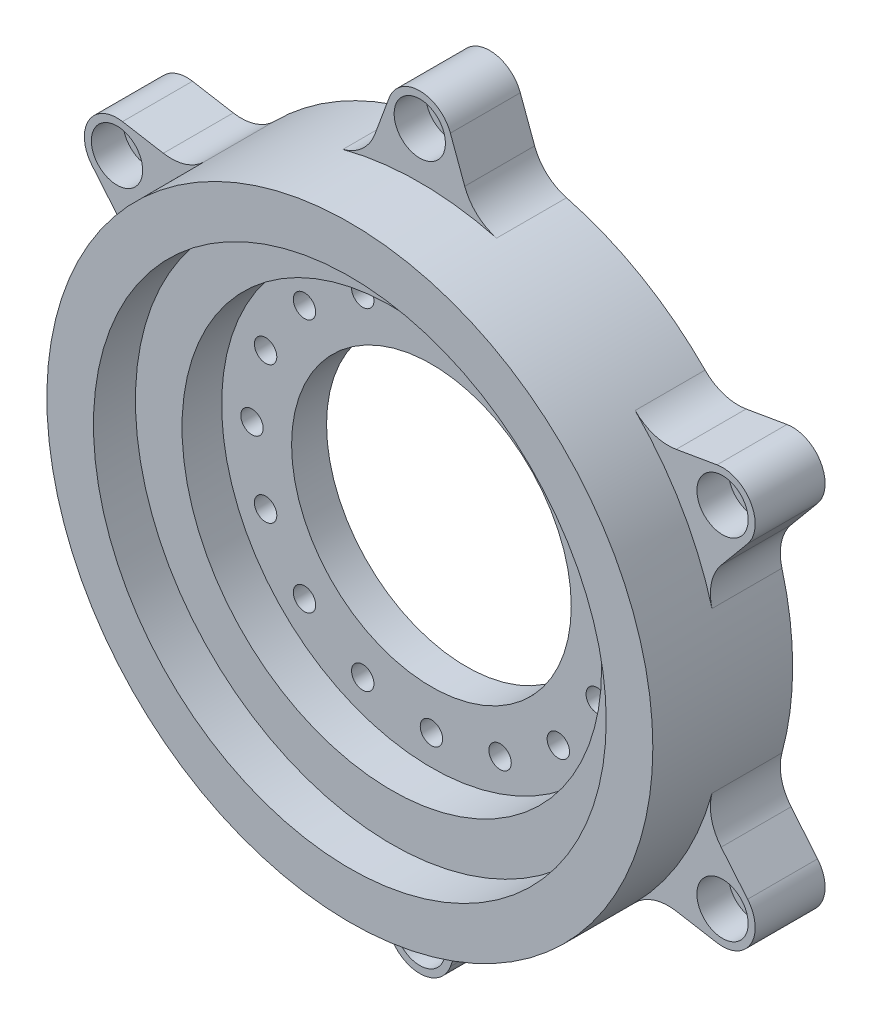
SolidWorks part; units mm, degrees
ref_plane "前视基准面" through (0, 0, 0) normal (0, 0, 1) x (1, 0, 0)
ref_plane "上视基准面" through (0, 0, 0) normal (0, 1, 0) x (1, 0, 0)
ref_plane "右视基准面" through (0, 0, 0) normal (1, 0, 0) x (0, 0, -1)
sketch "草图1" plane through (0, 0, 0) normal (0, 0, 1) x (1, 0, 0)
  circle A0 centre (0, 0) radius 65
  dimension "D1" = 130
extrude "凸台-拉伸1" add sketch "草图1" along normal blind 30
sketch "草图2" plane through (0, 0, 30) normal (0, 0, 1) x (1, 0, 0)
  circle A0 centre (0, 0) radius 55
  dimension "D1" = 110
extrude "切除-拉伸1" cut sketch "草图2" against normal blind 9
sketch "草图3" plane through (0, 0, 21) normal (0, 0, 1) x (1, 0, 0)
  circle A0 centre (0, 0) radius 45
  dimension "D1" = 90
extrude "切除-拉伸2" cut sketch "草图3" against normal blind 8.5
sketch "草图4" plane through (0, 0, 12.5) normal (0, 0, 1) x (1, 0, 0)
  circle A0 centre (0, 0) radius 30
  dimension "D1" = 60
extrude "切除-拉伸3" cut sketch "草图4" against normal blind 8.5
sketch "草图5" plane through (0, 0, 0) normal (0, 0, -1) x (-1, 0, 0)
  circle A0 centre (0, 0) radius 45
  dimension "D1" = 90
extrude "切除-拉伸4" cut sketch "草图5" against normal blind 5
hole_wizard "打孔尺寸(%根据)内六角圆柱头螺钉的类型1" positions "草图8" profile "草图7" counterbore size "M4" standard "GB" end condition through all
sketch "草图8" plane through (0, 0, 5) normal (0, 0, -1) x (-1, 0, 0)
  line L0 (0, 0) -> (0, 67.8808) construction
  circle A0 centre (0, 0) radius 38.5 construction
  point P0 (0, 38.5)
  dimension "D1" = 77
sketch "草图7" plane through (0, 38.5, 5) normal (1, 0, 0) x (0, 1, 0)
  line L0 (0, 0) -> (0, 25)
  line L1 (0, 25) -> (2.4, 25)
  line L3 (2.4, 25) -> (2.4, 1)
  line L4 (2.4, 1) -> (4, 1)
  line L5 (4, 1) -> (4, 0)
  line L7 (4, 0) -> (0, 0)
  line L11 (0, -6.35) -> (0, 107.95) construction
  dimension "通孔孔直径" = 4.8
  dimension "通孔孔深度" = 25
  dimension "柱形沉头孔直径" = 8
  dimension "柱形沉头孔深度" = 1
ref_axis "基准轴1" through (0, 0, 30) along (0, 0, -1)
pattern_circular "阵列(圆周)1" count 16 over 360 about axis through (0, 0, 30) along (0, 0, -1) of "打孔尺寸(%根据)内六角圆柱头螺钉的类型1"
sketch "草图9" plane through (0, 0, 0) normal (0, 0, -1) x (-1, 0, 0)
  line L0 (0, 82.5863) -> (0, -77.8427) construction
  line L1 (-6.5674, 77.4226) -> (-9.6426, 69.0861)
  line L2 (6.5674, 77.4226) -> (9.6426, 69.0861)
  circle A0 centre (0, 0) radius 75 construction
  arc A1 (6.5674, 77.4226) -> (-6.5674, 77.4226) centre (0, 75) ccw
  arc A3 (16.488, 62.874) -> (-16.488, 62.874) centre (0, 0) ccw
  arc A4 (-16.488, 62.874) -> (-9.6426, 69.0861) centre (-19.0247, 72.547) ccw
  arc A5 (16.488, 62.874) -> (9.6426, 69.0861) centre (19.0247, 72.547) cw
  dimension "D1" = 150
  dimension "D2" = 14
  dimension "D3" = 10
  dimension "D4" = 130
extrude "凸台-拉伸2" add sketch "草图9" against normal blind 15
hole_wizard "打孔尺寸(%根据)内六角圆柱头螺钉的类型2" positions "草图14" profile "草图13" counterbore size "M6" standard "GB" end condition through all
sketch "草图14" plane through (0, 0, 15) normal (0, 0, 1) x (1, 0, 0)
  line L0 (0, 0) -> (0, 87.1617) construction
  circle A0 centre (0, 0) radius 75 construction
  point P0 (0, 75)
  dimension "D1" = 150
sketch "草图13" plane through (0, 75, 15) normal (1, 0, 0) x (0, -1, 0)
  line L0 (0, 0) -> (0, 15)
  line L1 (0, 15) -> (3.5, 15)
  line L3 (3.5, 15) -> (3.5, 6.8)
  line L4 (3.5, 6.8) -> (5.5, 6.8)
  line L5 (5.5, 6.8) -> (5.5, 0)
  line L7 (5.5, 0) -> (0, 0)
  line L11 (0, -6.35) -> (0, 107.95) construction
  dimension "通孔孔直径" = 7
  dimension "通孔孔深度" = 15
  dimension "柱形沉头孔直径" = 11
  dimension "柱形沉头孔深度" = 6.8
pattern_circular "阵列(圆周)2" count 6 over 360 about axis through (0, 0, 30) along (0, 0, -1) of "凸台-拉伸2", "打孔尺寸(%根据)内六角圆柱头螺钉的类型2"
